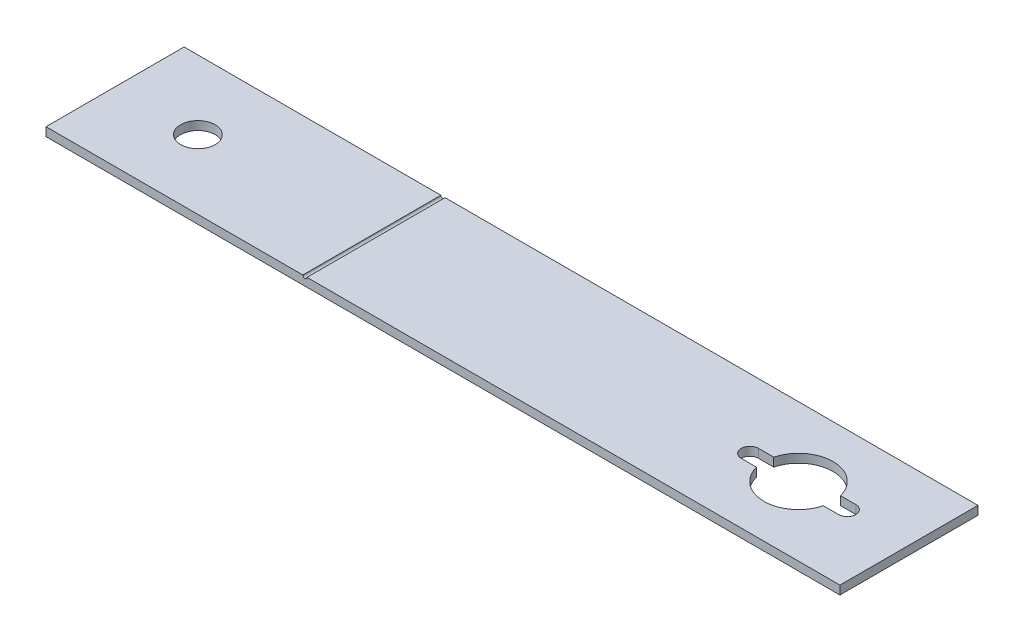
SolidWorks part; units mm, degrees
ref_plane "Front Plane" through (0, 0, 0) normal (0, 0, 1) x (1, 0, 0)
ref_plane "Top Plane" through (0, 0, 0) normal (0, 1, 0) x (1, 0, 0)
ref_plane "Right Plane" through (0, 0, 0) normal (1, 0, 0) x (0, 0, -1)
sketch "Sketch1" plane through (0, 0, 0) normal (0, 1, 0) x (1, 0, 0)
  line L1 (-73.025, -12.7) -> (73.025, -12.7)
  line L2 (-73.025, -12.7) -> (-73.025, 12.7)
  line L3 (-73.025, 12.7) -> (73.025, 12.7)
  line L4 (73.025, -12.7) -> (73.025, 12.7)
  line L5 (-73.025, -12.7) -> (73.025, 12.7) construction
  line L6 (-73.025, 12.7) -> (73.025, -12.7) construction
  point P0 (0, 0)
  dimension "D1" = 25.4
  dimension "D2" = 146.05
base flange "Base-Flange1" sketch "Sketch1" thickness 1.5875 reverse thickness direction no parameters "D1"=0.7366
sketch "Sketch6" plane through (0, 0, 0) normal (0, 1, 0) x (1, 0, 0)
  line L0 (-73.025, 12.7) -> (-73.025, -12.7) construction
  circle A0 centre (-57.785, 0) radius 3.175
  dimension "D1" = 6.35
  dimension "D2" = 15.24
extrude "Cut-Extrude1" cut sketch "Sketch6" against normal blind 2.54 normal cut yes
sketch "Sketch8" plane through (0, 0, 0) normal (0, 1, 0) x (1, 0, 0)
  line L0 (43.7515, 1.5875) -> (46.5566, 1.5875)
  line L1 (43.7515, -1.5875) -> (46.5566, -1.5875)
  line L2 (61.6585, 1.5875) -> (58.8534, 1.5875)
  line L3 (61.6585, -1.5875) -> (58.8534, -1.5875)
  line L4 (73.025, 12.7) -> (-73.025, 12.7) construction
  arc A0 (46.5566, -1.5875) -> (58.8534, -1.5875) centre (52.705, 0) ccw
  arc A1 (43.7515, 1.5875) -> (43.7515, -1.5875) centre (43.7515, 0) ccw
  arc A2 (61.6585, -1.5875) -> (61.6585, 1.5875) centre (61.6585, 0) ccw
  circle A3 centre (-57.785, 0) radius 3.175 construction
  arc A4 (58.8534, 1.5875) -> (46.5566, 1.5875) centre (52.705, 0) ccw
  point P16 (46.6094, 8.6084)
  point P19 (36.5313, 16.0933)
  dimension "D1" = 3.175
  dimension "D2" = 12.7
  dimension "D3" = 3.175
  dimension "D4" = 0
  dimension "D5" = 0
  dimension "D6" = 8.9535
  dimension "D7" = 8.9535
  dimension "D8" = 110.49
  dimension "D9" = 12.7
extrude "Cut-Extrude3" cut sketch "Sketch8" against normal blind 2.54 normal cut yes
sketch "Sketch9" plane through (0, 0, 0) normal (0, 1, 0) x (1, 0, 0)
  line L0 (-25.4, 12.7) -> (-25.4, -12.7)
  line L1 (73.025, 12.7) -> (-73.025, 12.7) construction
  line L2 (-73.025, -12.7) -> (73.025, -12.7) construction
  circle A0 centre (-57.785, 0) radius 3.175 construction
  dimension "D1" = 32.385
sketch "Sketch10" plane through (0, 0, 12.7) normal (0, 0, 1) x (1, 0, 0)
  line L0 (-73.025, 0) -> (73.025, 0) construction
  circle A0 centre (-25.3988, 0) radius 0.381
  dimension "D1" = 0.762
extrude "Cut-Extrude4" cut sketch "Sketch10" against normal blind 25.654 normal cut yes
sketch "Bend-Lines1" plane through (0, 0, 0) normal (0, 1, 0) x (1, 0, 0)
sketch "Bounding-Box1" plane through (0, 0, 0) normal (0, 1, 0) x (1, 0, 0)
sheet metal parameters "Sheet-Metal1" thickness 1.5875 parameters "D1"=0.7366
flat pattern "Flat-Pattern1" [suppressed]
sketch "Bend-Lines2" plane through (0, 0, 0) normal (0, 1, 0) x (1, 0, 0)
sketch "Bounding-Box2" [suppressed] plane through (0, 0, 0) normal (0, 1, 0) x (1, 0, 0)
sheet metal parameters "Sheet-Metal2" thickness 1.5875 parameters "D1"=0.7366
flat pattern "Flat-Pattern1"
sketch "Bend-Lines2" plane through (0, 0, 0) normal (0, 1, 0) x (1, 0, 0)
sketch "Bounding-Box2" [suppressed] plane through (0, 0, 0) normal (0, 1, 0) x (1, 0, 0)
sheet metal parameters "Sheet-Metal3" thickness 1.5875 parameters "D1"=0.7366
flat pattern "Flat-Pattern1"
sketch "Bend-Lines2" plane through (0, 0, 0) normal (0, 1, 0) x (1, 0, 0)
sketch "Bounding-Box2" [suppressed] plane through (0, 0, 0) normal (0, 1, 0) x (1, 0, 0)
sheet metal parameters "Sheet-Metal4" thickness 1.5875 parameters "D1"=0.7366
flat pattern "Flat-Pattern1"
sketch "Bend-Lines2" plane through (0, 0, 0) normal (0, 1, 0) x (1, 0, 0)
sketch "Bounding-Box2" [suppressed] plane through (0, 0, 0) normal (0, 1, 0) x (1, 0, 0)
